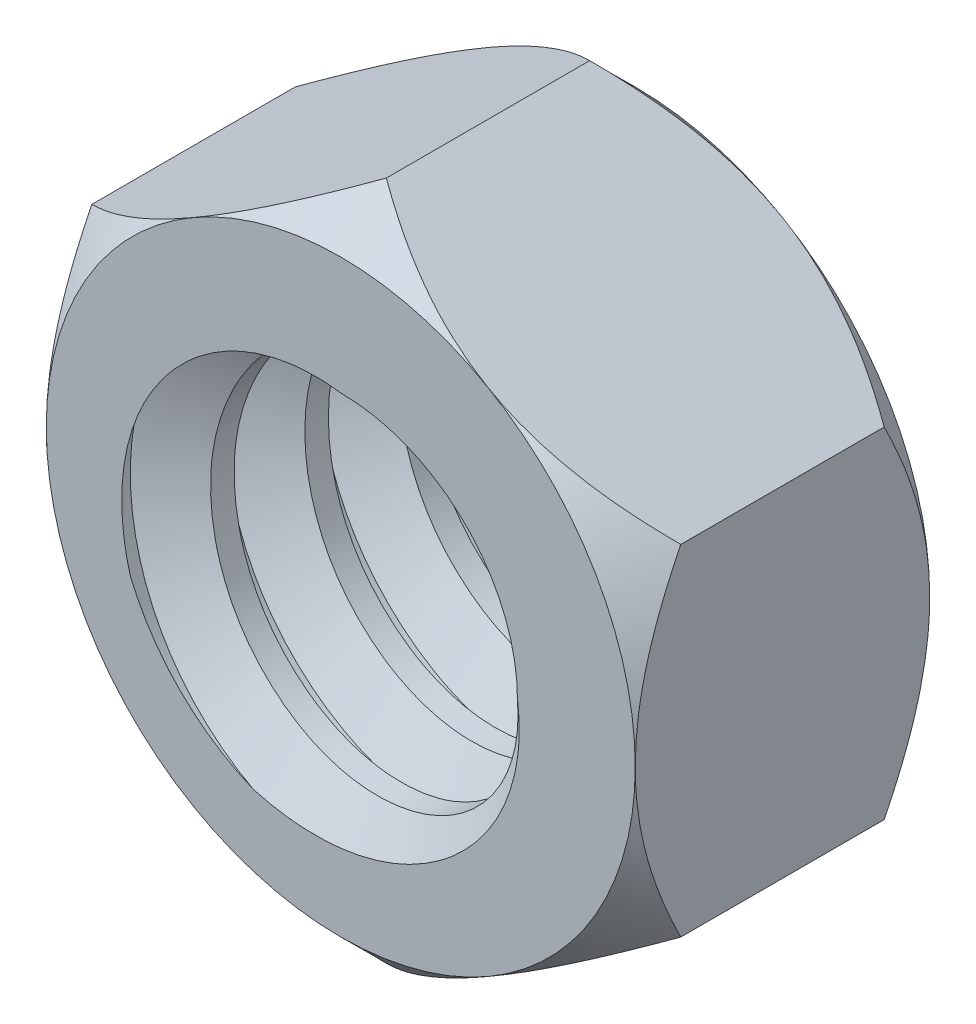
SolidWorks part; units mm, degrees
material "Cast Stainless Steel"
ref_plane "Front Plane" through (0, 0, 0) normal (0, 0, 1) x (1, 0, 0)
ref_plane "Top Plane" through (0, 0, 0) normal (0, 1, 0) x (1, 0, 0)
ref_plane "Right Plane" through (0, 0, 0) normal (1, 0, 0) x (0, 0, -1)
sketch "Sketch1" plane through (0, 0, 0) normal (0, 0, 1) x (1, 0, 0)
  line L0 (0, 0) -> (0, 3.9416) construction
  line L1 (0, 2.8868) -> (-2.5, 1.4434)
  line L2 (-2.5, 1.4434) -> (-2.5, -1.4434)
  line L3 (-2.5, -1.4434) -> (0, -2.8868)
  line L4 (0, -2.8868) -> (2.5, -1.4434)
  line L5 (2.5, -1.4434) -> (2.5, 1.4434)
  line L6 (2.5, 1.4434) -> (0, 2.8868)
  circle A0 centre (0, 0) radius 2.5 construction
  circle A1 centre (0, 0) radius 1.5
  dimension "D1" = 5
  dimension "D2" = 3
extrude "Boss-Extrude1" add sketch "Sketch1" along normal mid plane 2.5 contours L6 L1 L2 L3 L4 L5
sketch "Sketch8" plane through (0, 0, 1.25) normal (0, 0, 1) x (1, 0, 0)
  circle A0 centre (0, 0) radius 2.5
  dimension "D1" = 5
extrude "Cut-Extrude4" cut sketch "Sketch8" against normal blind 10 draft 45 flip side to cut
mirror "Mirror1" about plane through (0, 0, 0) normal (0, 0, 1) of "Cut-Extrude4"
extrude "Cut-Extrude5" cut sketch "Sketch1<4>" against normal blind 10 and the other way blind 10 contours A1
sketch "Sketch1<4>" plane through (0, 0, 0) normal (0, 0, 1) x (1, 0, 0) same geometry as "Sketch1"
thread "Thread2" pitch 0.8 method cut profile "Thread Profile3" start angle 0, offset 1, length 10, pitch 0.8, diameter 3
ref_plane "Plane3" through (-1.5, 0, 2.25) normal (0, -1, 0) x (-1, 0, 0)
sketch "Thread Profile3" plane through (-1.5, 0, 2.25) normal (0, -1, 0) x (-1, 0, 0)
  line L0 (0, 0) -> (0, 0.8) construction
  line L1 (0, 0) -> (0.433, 0.25)
  line L2 (0.433, 0.25) -> (0.433, 0.35)
  line L3 (0.433, 0.35) -> (0, 0.6)
  line L4 (0.433, 0.3) -> (0, 0.3) construction
  line L11 (0, 0) -> (0, 0.6)
  point P2 (0, 0)
  dimension "Pitch" = 0.8
  dimension "Profile_Angle" = 60
  dimension "Profile_Land" = 0.1
  dimension "Profile_Height" = 0.433
scale "Scale1" scale about centroid uniform scaling yes scale factor 1.666667
